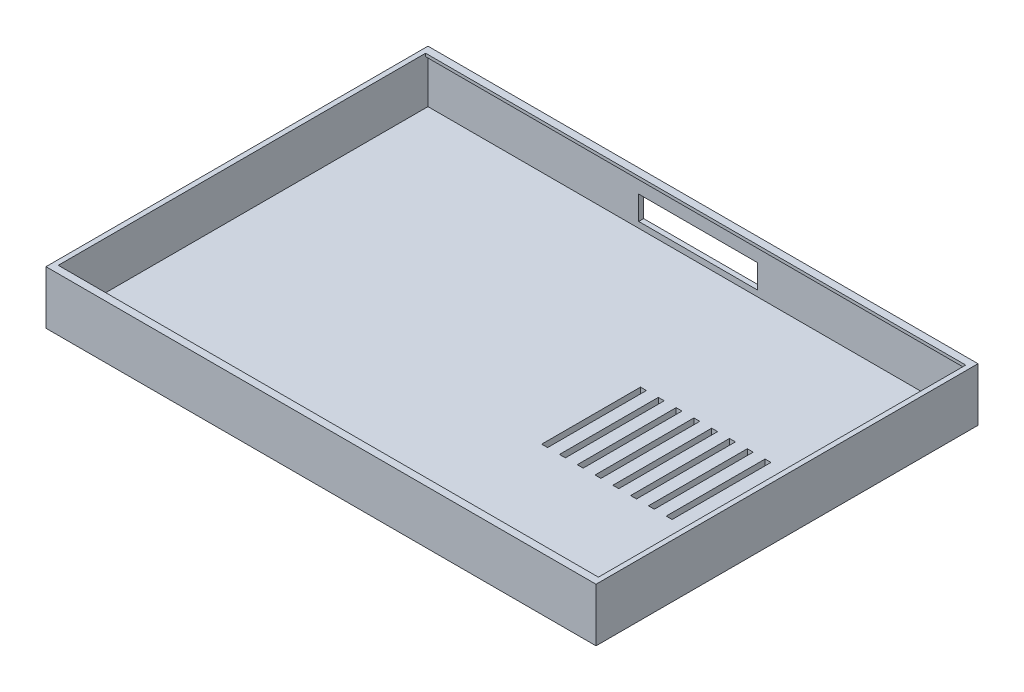
SolidWorks part; units mm, degrees
ref_plane "Front Plane" through (0, 0, 0) normal (0, 0, 1) x (1, 0, 0)
ref_plane "Top Plane" through (0, 0, 0) normal (0, 1, 0) x (1, 0, 0)
ref_plane "Right Plane" through (0, 0, 0) normal (1, 0, 0) x (0, 0, -1)
sketch "Sketch1" plane through (0, 0, 0) normal (0, 1, 0) x (1, 0, 0)
  line L1 (-139.1, -96.6) -> (139.1, -96.6)
  line L2 (-139.1, -96.6) -> (-139.1, 96.6)
  line L3 (-139.1, 96.6) -> (139.1, 96.6)
  line L4 (139.1, -96.6) -> (139.1, 96.6)
  line L5 (-139.1, -96.6) -> (139.1, 96.6) construction
  line L6 (-139.1, 96.6) -> (139.1, -96.6) construction
  point P0 (0, 0)
  dimension "D1" = 278.2
  dimension "D2" = 193.2
extrude "Shell Block" add sketch "Sketch1" along normal blind 27
ref_plane "Shell Front" through (0, 27, 0) normal (0, 1, 0) x (1, 0, 0)
sketch "Sketch2" plane through (0, 27, 0) normal (0, 1, 0) x (1, 0, 0)
  line L1 (-136.6, -92.9) -> (136.6, -92.9)
  line L2 (-136.6, -92.9) -> (-136.6, 92.9)
  line L3 (-136.6, 92.9) -> (136.6, 92.9)
  line L4 (136.6, -92.9) -> (136.6, 92.9)
  line L5 (-136.6, -92.9) -> (136.6, 92.9) construction
  line L6 (-136.6, 92.9) -> (136.6, -92.9) construction
  point P0 (0, 0)
  dimension "D1" = 273.2
  dimension "D2" = 185.8
extrude "Front Opening" cut sketch "Sketch2" against normal blind 1.5
ref_plane "Under Lip" through (0, 25.5, 0) normal (0, 1, 0) x (1, 0, 0)
sketch "Sketch3" plane through (0, 25.5, 0) normal (0, 1, 0) x (1, 0, 0)
  line L1 (-136.6, -94.1) -> (136.6, -94.1)
  line L2 (-136.6, -94.1) -> (-136.6, 94.1)
  line L3 (-136.6, 94.1) -> (136.6, 94.1)
  line L4 (136.6, -94.1) -> (136.6, 94.1)
  line L5 (-136.6, -94.1) -> (136.6, 94.1) construction
  line L6 (-136.6, 94.1) -> (136.6, -94.1) construction
  point P0 (0, 0)
  dimension "D1" = 273.2
  dimension "D2" = 188.2
extrude "Display Pocket" cut sketch "Sketch3" against normal blind 22.5
ref_plane "Back Inner" through (0, 3, 0) normal (0, 1, 0) x (1, 0, 0)
sketch "Sketch4" plane through (0, 3, 0) normal (0, 1, 0) x (1, 0, 0)
  line L1 (40, -25) -> (43, -25)
  line L2 (40, -25) -> (40, 25)
  line L3 (40, 25) -> (43, 25)
  line L4 (43, -25) -> (43, 25)
  line L5 (49, -25) -> (52, -25)
  line L6 (49, -25) -> (49, 25)
  line L7 (49, 25) -> (52, 25)
  line L8 (52, -25) -> (52, 25)
  line L9 (58, -25) -> (61, -25)
  line L10 (58, -25) -> (58, 25)
  line L11 (58, 25) -> (61, 25)
  line L12 (61, -25) -> (61, 25)
  line L13 (67, -25) -> (70, -25)
  line L14 (67, -25) -> (67, 25)
  line L15 (67, 25) -> (70, 25)
  line L16 (70, -25) -> (70, 25)
  line L17 (76, -25) -> (79, -25)
  line L18 (76, -25) -> (76, 25)
  line L19 (76, 25) -> (79, 25)
  line L20 (79, -25) -> (79, 25)
  line L21 (85, -25) -> (88, -25)
  line L22 (85, -25) -> (85, 25)
  line L23 (85, 25) -> (88, 25)
  line L24 (88, -25) -> (88, 25)
  line L25 (94, -25) -> (97, -25)
  line L26 (94, -25) -> (94, 25)
  line L27 (94, 25) -> (97, 25)
  line L28 (97, -25) -> (97, 25)
  line L29 (103, -25) -> (106, -25)
  line L30 (103, -25) -> (103, 25)
  line L31 (103, 25) -> (106, 25)
  line L32 (106, -25) -> (106, 25)
extrude "Vent Slots" cut sketch "Sketch4" against normal blind 4
sketch "Sketch5" plane through (0, 0, 0) normal (0, 0, 1) x (1, 0, 0)
  line L1 (-30, 6) -> (30, 6)
  line L2 (-30, 6) -> (-30, 18)
  line L3 (-30, 18) -> (30, 18)
  line L4 (30, 6) -> (30, 18)
extrude "Cable Exit" cut sketch "Sketch5" against normal blind 97.6
sketch "Sketch6" plane through (0, 0, 0) normal (0, 0, 1) x (1, 0, 0)
  line L0 (-15, 0) -> (15, 0)
  line L1 (-139.1, 0) -> (139.1, 0) construction
  line L2 (15, 0) -> (20, -5)
  line L3 (20, -5) -> (-19, -5)
  line L4 (-19, -5) -> (-15, 0)
sketch "Sketch7" plane through (0, 0, 0) normal (0, 0, 1) x (1, 0, 0)
  line L0 (-15, 0.5) -> (15, 0.5)
  line L1 (15, 0.5) -> (19, -6)
  line L2 (19, -6) -> (-19, -6)
  line L3 (-19, -6) -> (-15, 0.5)
extrude "Dovetail Rail" add sketch "Sketch7" along normal mid plane 90
equation "\"DispL\" = 272.0"
equation "\"DispW\" = 187.0"
equation "\"DispT\" = 20.0"
equation "\"Clr\" = 0.6"
equation "\"Wall\" = 2.5"
equation "\"BackT\" = 3.0"
equation "\"CableRoom\" = 4.0"
equation "\"LipW\" = 1.2"
equation "\"LipT\" = 1.5"
equation "\"RailW\" = 30.0"
equation "\"RailW2\" = 38.0"
equation "\"RailH\" = 6.0"
equation "\"RailL\" = 90.0"
equation "\"CableW\" = 60.0"
equation "\"CableH\" = 12.0"
equation "\"ShellL\" = \"DispL\" + 2 * \"Clr\" + 2 * \"Wall\""
equation "\"ShellW\" = \"DispW\" + 2 * \"Clr\" + 2 * \"Wall\""
equation "\"ShellH\" = \"BackT\" + \"DispT\" + \"CableRoom\""
equation "\"D1@Sketch1\" = \"ShellL\""
equation "\"D2@Sketch1\" = \"ShellW\""
equation "\"D1@Shell Block\" = \"ShellH\""
equation "\"D1@Shell Front\" = \"ShellH\""
equation "\"D1@Sketch2\" = \"DispL\" + 2 * \"Clr\""
equation "\"D2@Sketch2\" = \"DispW\" + 2 * \"Clr\" - 2 * \"LipW\""
equation "\"D1@Front Opening\" = \"LipT\""
equation "\"D1@Under Lip\" = \"ShellH\" - \"LipT\""
equation "\"D1@Sketch3\" = \"DispL\" + 2 * \"Clr\""
equation "\"D2@Sketch3\" = \"DispW\" + 2 * \"Clr\""
equation "\"D1@Display Pocket\" = \"ShellH\" - \"LipT\" - \"BackT\""
equation "\"D1@Back Inner\" = \"BackT\""
equation "\"D1@Dovetail Rail\" = \"RailL\""
